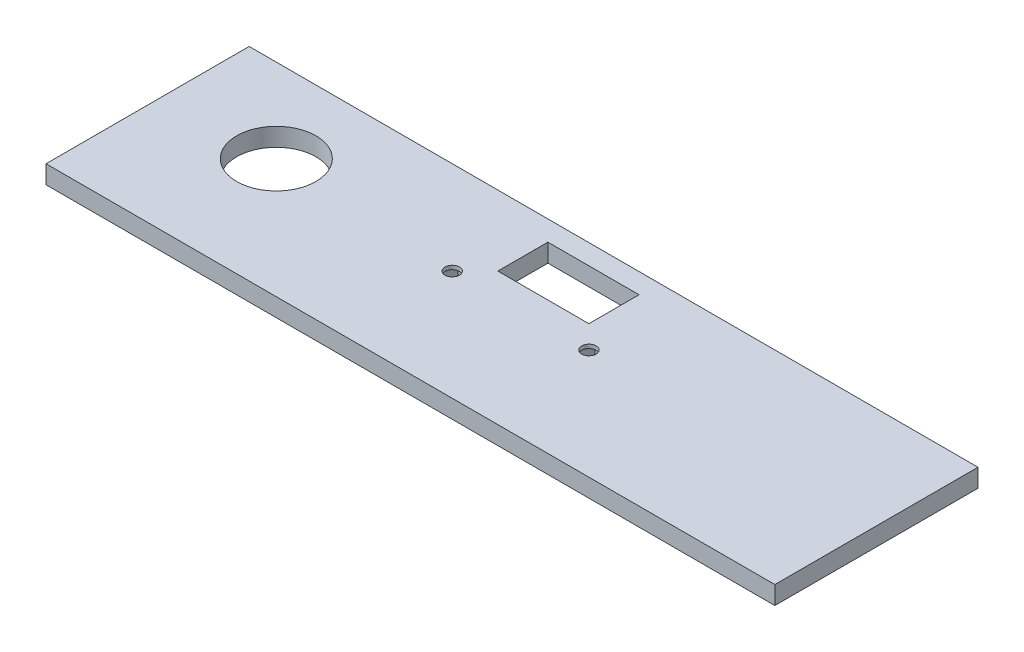
SolidWorks part; units mm, degrees
ref_plane "Front" through (0, 0, 0) normal (0, 0, 1) x (1, 0, 0)
ref_plane "Top" through (0, 0, 0) normal (0, 1, 0) x (1, 0, 0)
ref_plane "Right" through (0, 0, 0) normal (1, 0, 0) x (0, 0, -1)
sketch "Sketch2" plane through (0, 0, 0) normal (0, 1, 0) x (1, 0, 0)
  line L1 (-101.6, 28.321) -> (101.6, 28.321)
  line L2 (-101.6, 28.321) -> (-101.6, -28.321)
  line L3 (-101.6, -28.321) -> (101.6, -28.321)
  line L4 (101.6, 28.321) -> (101.6, -28.321)
  line L5 (-101.6, 28.321) -> (101.6, -28.321) construction
  line L6 (-101.6, -28.321) -> (101.6, 28.321) construction
  line L8 (-70.7277, 5.0127) -> (-70.7277, 16.0617) construction
  line L10 (0, -55) -> (0, 55) construction
  line L11 (-12.7, 22.712) -> (12.7, 22.712)
  line L12 (-12.7, 22.712) -> (-12.7, 8.742)
  line L13 (-12.7, 8.742) -> (12.7, 8.742)
  line L14 (12.7, 22.712) -> (12.7, 8.742)
  line L15 (-12.7, 22.712) -> (12.7, 8.742) construction
  line L16 (-12.7, 8.742) -> (12.7, 22.712) construction
  circle A0 centre (-70.7277, 5.0127) radius 11.049
  circle A1 centre (-19.05, 2.392) radius 2
  circle A2 centre (19.05, 2.392) radius 2
  point P0 (0, 0)
  point P13 (-70.7277, 17.7664)
  point P14 (0, 15.727)
  dimension "D1" = 22.098
  dimension "D8" = 4
  dimension "D4" = 25.4
  dimension "D5" = 13.97
  dimension "D6" = 203.2
  dimension "D7" = 56.642
  dimension "D9" = 6.35
  dimension "D10" = 19.05
extrude "Boss-Extrude1" add sketch "Sketch2" along normal blind 5.08 contours L4 L1 L2 L3 A0 region at (2.5242, 0, 0.7038)
sketch "Sketch4" plane through (0, 0, 0) normal (0, -1, 0) x (1, 0, 0)
  line L0 (0, -55) -> (0, 55) construction
  line L1 (-16.7695, -6.342) -> (-14.4889, -2.392)
  line L2 (-14.4889, -2.392) -> (-16.7695, 1.558)
  line L3 (-16.7695, 1.558) -> (-21.3305, 1.558)
  line L4 (101.6, -28.321) -> (101.6, 28.321)
  line L5 (101.6, 28.321) -> (-101.6, 28.321)
  line L6 (-101.6, 28.321) -> (-101.6, -28.321)
  line L7 (-101.6, -28.321) -> (101.6, -28.321)
  line L8 (101.6, -28.321) -> (101.6, 28.321)
  line L9 (101.6, 28.321) -> (-101.6, 28.321)
  line L10 (-101.6, 28.321) -> (-101.6, -28.321)
  line L11 (-101.6, -28.321) -> (101.6, -28.321)
  line L12 (-21.3305, 1.558) -> (-23.6111, -2.392)
  line L13 (-23.6111, -2.392) -> (-21.3305, -6.342)
  line L14 (-21.3305, -6.342) -> (-16.7695, -6.342)
  line L15 (16.7695, -6.342) -> (14.4889, -2.392)
  line L16 (21.3305, -6.342) -> (16.7695, -6.342)
  line L17 (23.6111, -2.392) -> (21.3305, -6.342)
  line L18 (21.3305, 1.558) -> (23.6111, -2.392)
  line L19 (16.7695, 1.558) -> (21.3305, 1.558)
  line L20 (14.4889, -2.392) -> (16.7695, 1.558)
  line L21 (101.6, 28.321) -> (101.6, -28.321)
  line L22 (-101.6, -28.321) -> (-101.6, 28.321)
  circle A0 centre (19.05, -2.392) radius 2 construction
  circle A1 centre (-19.05, -2.392) radius 2 construction
  circle A2 centre (19.05, -2.392) radius 2
  circle A3 centre (-19.05, -2.392) radius 2
  circle A4 centre (-19.05, -2.392) radius 3.95 construction
  dimension "D2" = 7.9
  dimension "D1" = 0
extrude "Cut-Extrude1" cut sketch "Sketch4" against normal blind 4 contours L2 L3 L12 L13 L14 L1 | L20 L19 L18 L17 L16 L15
sketch "Sketch5" plane through (0, 0, 28.321) normal (0, 0, 1) x (1, 0, 0)
  line L0 (0, -55) -> (0, 55) construction
  line L1 (-66.675, 5.08) -> (-60.325, 5.08)
  line L2 (-66.675, 5.08) -> (-66.675, -7.62)
  line L3 (-66.675, -7.62) -> (-60.325, -7.62)
  line L4 (-60.325, 5.08) -> (-60.325, -7.62)
  line L5 (66.675, -7.62) -> (60.325, -7.62)
  line L6 (60.325, 5.08) -> (60.325, -7.62)
  line L7 (66.675, 5.08) -> (60.325, 5.08)
  line L8 (-101.6, 0) -> (101.6, 0)
  line L9 (101.6, 0) -> (101.6, 5.08)
  line L10 (101.6, 5.08) -> (-101.6, 5.08)
  line L11 (-101.6, 5.08) -> (-101.6, 0)
  line L12 (-101.6, 0) -> (101.6, 0)
  line L13 (101.6, 0) -> (101.6, 5.08)
  line L14 (101.6, 5.08) -> (-101.6, 5.08)
  line L15 (-101.6, 5.08) -> (-101.6, 0)
  line L16 (66.675, 5.08) -> (66.675, -7.62)
  circle A0 centre (-63.5, -3.81) radius 1.5
  circle A1 centre (63.5, -3.81) radius 1.5
  point P18 (-63.5, -7.62)
  line M13 (-101.6, 0) -> (101.6, 0)
  line M15 (101.6, 5.08) -> (-101.6, 5.08)
  dimension "D4" = 3
  dimension "D2" = 6.35
  dimension "D3" = 12.7
  dimension "D5" = 3.81
  dimension "D6" = 63.5
  dimension "D1" = 0
extrude "Boss-Extrude2" add sketch "Sketch5" along normal blind 3.81 from surface contours L4 L2 L3 A0 M13 | L4 L2 M15 M13 | L16 L6 M15 M13 | L16 L6 L5 A1 M13 region at (-63.5, 2.54, 28.321) region at (-63.5, -0.0992, 28.321) region at (63.5, 2.54, 28.321) region at (63.5, -0.0992, 28.321) starting at face at (0, 2.54, -28.321)
